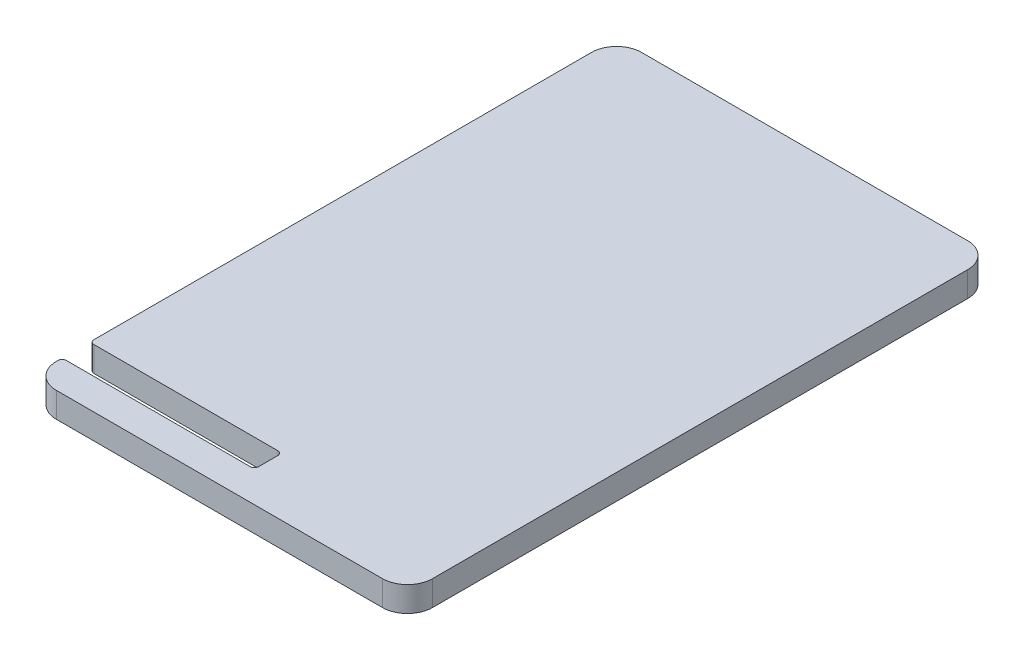
SolidWorks part; units mm, degrees
ref_plane "Alzado" through (0, 0, 0) normal (0, 0, 1) x (1, 0, 0)
ref_plane "Planta" through (0, 0, 0) normal (0, 1, 0) x (1, 0, 0)
ref_plane "Vista lateral" through (0, 0, 0) normal (1, 0, 0) x (0, 0, -1)
sketch "Croquis1" plane through (0, 0, 0) normal (0, 1, 0) x (1, 0, 0)
  line L1 (-22.5, 35.3062) -> (22.5, 35.3062)
  line L2 (-22.5, 35.3062) -> (-22.5, -34.6938)
  line L3 (-22.5, -34.6938) -> (22.5, -34.6938)
  line L4 (22.5, 35.3062) -> (22.5, -34.6938)
  dimension "D1" = 22.5
  dimension "D2" = 45
  dimension "D3" = 35.3062
  dimension "D4" = 70
extrude "Saliente-Extruir1" add sketch "Croquis1" along normal blind 3
sketch "Croquis2" plane through (0, 3, 0) normal (0, 1, 0) x (1, 0, 0)
  line L0 (-22.5, 35.3062) -> (-22.5, -34.6938) construction
  line L1 (-22.5, -27.7) -> (0.5, -27.7)
  line L2 (-22.5, -27.7) -> (-22.5, -31)
  line L3 (-22.5, -31) -> (0.5, -31)
  line L4 (0.5, -27.7) -> (0.5, -31)
  dimension "D1" = 3.3
  dimension "D2" = 31
  dimension "D3" = 23
extrude "Cortar-Extruir1" cut sketch "Croquis2" against normal up to surface (3 mm away) up to face at (0, 0, -0.3062)
fillet "Redondeo1" radius 3 4 edges at (-22.5, 1.5, 34.6938) (22.5, 1.5, 34.6938) (-22.5, 1.5, -35.3062) (22.5, 1.5, -35.3062)
fillet "Redondeo2" radius 0.5 4 edges at (-22.5, 1.5, 31) (0.5, 1.5, 31) (0.5, 1.5, 27.7) (-22.5, 1.5, 27.7)
